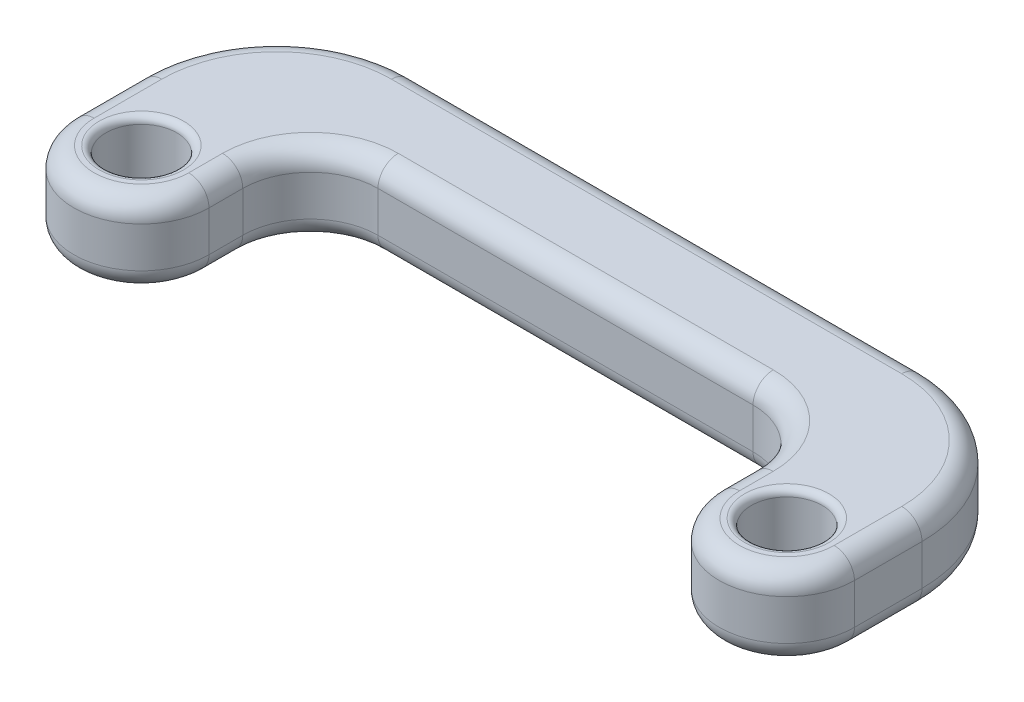
SolidWorks part; units mm, degrees
ref_plane "Front Plane" through (0, 0, 0) normal (0, 0, 1) x (1, 0, 0)
ref_plane "Top Plane" through (0, 0, 0) normal (0, 1, 0) x (1, 0, 0)
ref_plane "Right Plane" through (0, 0, 0) normal (1, 0, 0) x (0, 0, -1)
sketch "Sketch7" plane through (0, 0, 0) normal (0, 1, 0) x (1, 0, 0)
  line L2 (-105.5, 0) -> (-105.5, 30)
  line L3 (-85.5, 0) -> (-85.5, 15)
  line L4 (-105.5, 30) -> (-85.5, 30)
  line L6 (-85.5, 30) -> (10, 30)
  line L7 (-85.5, 15) -> (-10, 15)
  line L10 (10, 0) -> (10, 30.0013)
  line L11 (-10, 0) -> (-10, 15)
  line L12 (10, 30.0013) -> (-10, 30.0013)
  line L13 (-10, 30) -> (-10, 30.0013)
  arc A0 (-10, 0) -> (10, 0) centre (0, 0) ccw
  arc A1 (-105.5, 0) -> (-85.5, 0) centre (-95.5, 0) ccw
  circle A2 centre (-95.5, 0) radius 5
extrude "Boss-Extrude5" add sketch "Sketch7" along normal blind 12 contours L2 A1 L3 L7 L11 A0 L10 L6 L4 A2 region at (-46.2897, 0, -16.412)
sketch "Sketch8" plane through (0, 12, 0) normal (0, 1, 0) x (1, 0, 0)
  circle A0 centre (0, 0) radius 6
fillet "Fillet2" radius 20 2 edges at (10, 6, -30) (-105.5, 6, -30)
fillet "Fillet3" radius 10 2 edges at (-10, 6, -15) (-85.5, 6, -15)
fillet "Fillet5" radius 3 24 edges at (-47.75, 12, -30) (4.1421, 12, -24.1421) (10, 12, -5) (0, 12, 10) (-10, 12, -2.5) (-12.9289, 12, -12.0711) (-47.75, 12, -15) (-82.5711, 12, -12.0711) (-85.5, 12, -2.5) (-95.5, 12, 10) (-105.5, 12, -5) (-105.5, 0, -5) (-95.5, 0, 10) (-85.5, 0, -2.5) (-82.5711, 0, -12.0711) (-47.75, 0, -15) (-12.9289, 0, -12.0711) (-10, 0, -2.5) (0, 0, 10) (10, 0, -5) (4.1421, 0, -24.1421) (-47.75, 0, -30) (-99.6421, 12, -24.1421) (-99.6421, 0, -24.1421)
sketch "Sketch11" plane through (0, 0, 0) normal (0, -1, 0) x (1, 0, 0)
  circle A0 centre (-95.5, 0) radius 5.25
  circle A1 centre (0, 0) radius 5.25
extrude "Cut-Extrude1" cut sketch "Sketch11" against normal blind 25
fillet "Fillet6" radius 1 4 edges at (-95.5, 12, 5.25) (-95.5, 0, -5.25) (0, 12, 5.25) (0, 0, -5.25)
